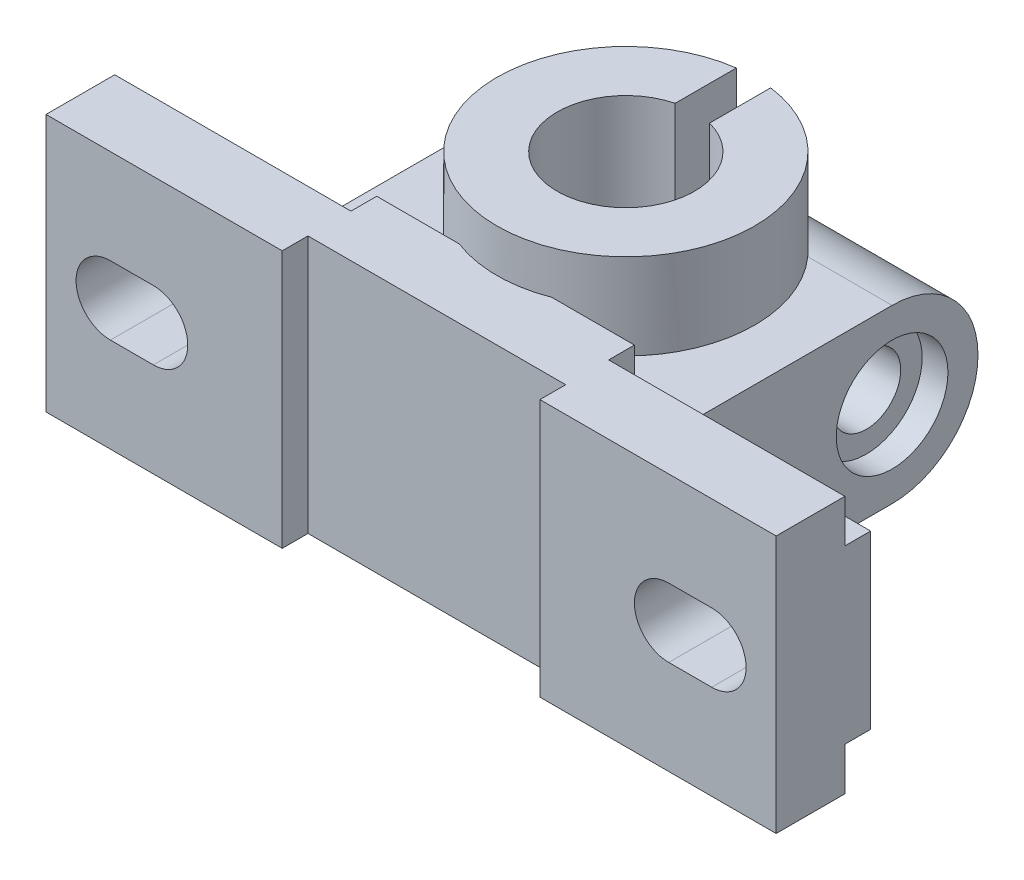
SolidWorks part; units mm, degrees
ref_plane "前视基准面" through (0, 0, 0) normal (0, 0, 1) x (1, 0, 0)
ref_plane "上视基准面" through (0, 0, 0) normal (0, 1, 0) x (1, 0, 0)
ref_plane "右视基准面" through (0, 0, 0) normal (1, 0, 0) x (0, 0, -1)
other "Configuration Table"
sketch "草图1" plane through (0, 0, 0) normal (0, 0, 1) x (1, 0, 0)
  line L1 (-42.5, -15) -> (42.5, -15)
  line L2 (-42.5, -15) -> (-42.5, 15)
  line L3 (-42.5, 15) -> (42.5, 15)
  line L4 (42.5, -15) -> (42.5, 15)
  line L5 (-42.5, -15) -> (42.5, 15) construction
  line L6 (-42.5, 15) -> (42.5, -15) construction
  point P0 (0, 0)
extrude "凸台-拉伸1" add sketch "草图1" along normal blind 11
sketch "草图2" plane through (0, 0, 0) normal (0, 0, 1) x (1, 0, 0)
  line L0 (-15, 15) -> (-15, 10)
  line L1 (42.5, 15) -> (-42.5, 15) construction
  line L2 (-15, 10) -> (-42.5, 10)
  line L3 (-42.5, 15) -> (-42.5, -15) construction
  line L4 (0, 0) -> (26.3616, 0) construction
  line L5 (0, 0) -> (0, -11.1958) construction
  line L6 (-15, 15) -> (-42.5, 15)
  line L7 (-42.5, 15) -> (-42.5, 10)
  line L8 (42.5, 15) -> (42.5, 10)
  line L9 (15, 15) -> (42.5, 15)
  line L10 (15, 10) -> (42.5, 10)
  line L11 (15, 15) -> (15, 10)
  line L12 (15, -15) -> (15, -10)
  line L13 (15, -10) -> (42.5, -10)
  line L14 (15, -15) -> (42.5, -15)
  line L15 (42.5, -15) -> (42.5, -10)
  line L16 (-42.5, -15) -> (-42.5, -10)
  line L17 (-15, -15) -> (-42.5, -15)
  line L18 (-15, -10) -> (-42.5, -10)
  line L19 (-15, -15) -> (-15, -10)
extrude "切除-拉伸3" cut sketch "草图2" along normal blind 3
sketch "草图6" plane through (0, 0, 0) normal (0, 0, 1) x (1, 0, 0)
  line L0 (0.091, 0) -> (-45.213, 0) construction
  line L1 (0, 0) -> (0, 14.7239) construction
  line L2 (-42.5, 0) -> (-35, 0)
  line L3 (-42.5, 10) -> (-42.5, -10) construction
  line L4 (-35, 0) -> (-30, 0)
  line L5 (-35, 0) -> (-30, 0) construction
  line L6 (-35, 4) -> (-30, 4)
  line L7 (-35, -4) -> (-30, -4)
  line L8 (-0.091, 0) -> (45.213, 0) construction
  line L9 (35, 0) -> (30, 0)
  line L10 (42.5, 0) -> (35, 0)
  line L11 (35, 0) -> (30, 0) construction
  line L12 (35, 4) -> (30, 4)
  line L13 (35, -4) -> (30, -4)
  arc A0 (-35, 4) -> (-35, -4) centre (-35, 0) ccw
  arc A1 (-30, -4) -> (-30, 4) centre (-30, 0) ccw
  arc A2 (35, 4) -> (35, -4) centre (35, 0) cw
  arc A3 (30, -4) -> (30, 4) centre (30, 0) cw
  point P2 (-32.5, 0)
  point P19 (32.5, 0)
extrude "切除-拉伸5" cut sketch "草图6" along normal blind 33 contours L7 A1 L6 A0 | A3 L13 A2 L12 region at (-32.5, 3.8474, 0) region at (37.7205, 2.7205, 0)
sketch "草图8" plane through (0, 0, 0) normal (0, 1, 0) x (1, 0, 0)
  line L0 (0, -11) -> (0, 14)
  line L1 (42.5, -11) -> (-42.5, -11) construction
  line L2 (15, 14) -> (15, 0)
  line L3 (-15, 14) -> (-15, 0)
  line L4 (-15, 0) -> (-5.3852, 0)
  line L5 (5.3852, 0) -> (15, 0)
  circle A0 centre (0, 14) radius 8
  circle A1 centre (0, 14) radius 15
extrude "凸台-拉伸6" add sketch "草图8" along normal mid plane 40 contours A1 A0 region at (-2.6612, 0, 0.3307)
sketch "草图9" plane through (0, 0, 0) normal (0, 1, 0) x (1, 0, 0)
  line L0 (0, 0) -> (0, 38.8774)
  line L2 (-2, 42.2039) -> (2, 42.2039)
  line L3 (-2, 42.2039) -> (-2, 20.4687)
  line L4 (-2, 20.4687) -> (2, 20.4687)
  line L5 (2, 42.2039) -> (2, 20.4687)
  line L6 (-2, 42.2039) -> (2, 20.4687) construction
  line L7 (-2, 20.4687) -> (2, 42.2039) construction
  point P3 (0, 31.3363)
extrude "切除-拉伸6" cut sketch "草图9" against normal mid plane 40 contours L5 L2 L3 L4 region at (0, 0, -41.9829)
sketch "草图10" plane through (0, 0, 0) normal (1, 0, 0) x (0, 0, -1)
  line L0 (-11, 0) -> (24, 0)
  line L1 (-11, -15) -> (-11, 15) construction
  line L2 (24, 10) -> (0, 10)
  line L3 (24, -10) -> (0, -10)
  line L4 (0, -15) -> (0, 15) construction
  line L5 (0, -10) -> (0, 10)
  circle A0 centre (24, 0) radius 4
  circle A1 centre (24, 0) radius 10
extrude "凸台-拉伸7" add sketch "草图10" along normal mid plane 42 contours A1 A0 | A1 L2 L5 L0 | A1 L0 L5 L3 region at (0, 5.3677, -8.2273) region at (0, -5.3677, -8.2273) region at (0, 6.8711, -17.1289)
sketch "草图11" plane through (0, 0, 0) normal (1, 0, 0) x (0, 0, -1)
  circle A0 centre (24, 0) radius 6.5
extrude "切除-拉伸9" cut sketch "草图11" against normal mid plane 81
sketch "草图13" plane through (0, 0, 0) normal (1, 0, 0) x (0, 0, -1)
  circle A0 centre (24, 0) radius 6.5
extrude "凸台-拉伸8" add sketch "草图13" along normal mid plane 36
sketch "草图14" plane through (0, 0, 0) normal (1, 0, 0) x (0, 0, -1)
  circle A0 centre (24, 0) radius 4
extrude "切除-拉伸10" cut sketch "草图14" against normal mid plane 36
sketch "草图15" plane through (0, 0, 0) normal (0, 1, 0) x (1, 0, 0)
  circle A0 centre (0, 14) radius 8
extrude "切除-拉伸11" cut sketch "草图15" against normal mid plane 36
sketch "草图16" plane through (0, 0, 0) normal (0, 1, 0) x (1, 0, 0)
  line L0 (-2, 34) -> (2, 34)
  line L3 (-2, 34) -> (-2, 21.746)
  line L5 (2, 34) -> (2, 21.746)
  line L8 (21, 34) -> (-21, 34) construction
  arc A0 (2, 21.746) -> (-2, 21.746) centre (0, 14) ccw
extrude "切除-拉伸12" cut sketch "草图16" against normal mid plane 36
sketch "草图19" plane through (0, 0, 0) normal (0, 1, 0) x (1, 0, 0)
  line L0 (0, 0) -> (0, -17.1207)
  line L1 (42.5, -11) -> (-42.5, -11) construction
  line L2 (15, -11) -> (-15, -11)
  line L3 (15, -11) -> (15, -8)
  line L4 (15, -8) -> (-15, -8)
  line L5 (-15, -11) -> (-15, -8)
  line L6 (15, -11) -> (-15, -8) construction
  line L7 (15, -8) -> (-15, -11) construction
  point P3 (0, -9.5)
  dimension "D1" = 30
  dimension "D2" = 3
extrude "切除-拉伸13" cut sketch "草图19" against normal through all both and the other way through all contours L4 L5 L2 L3
